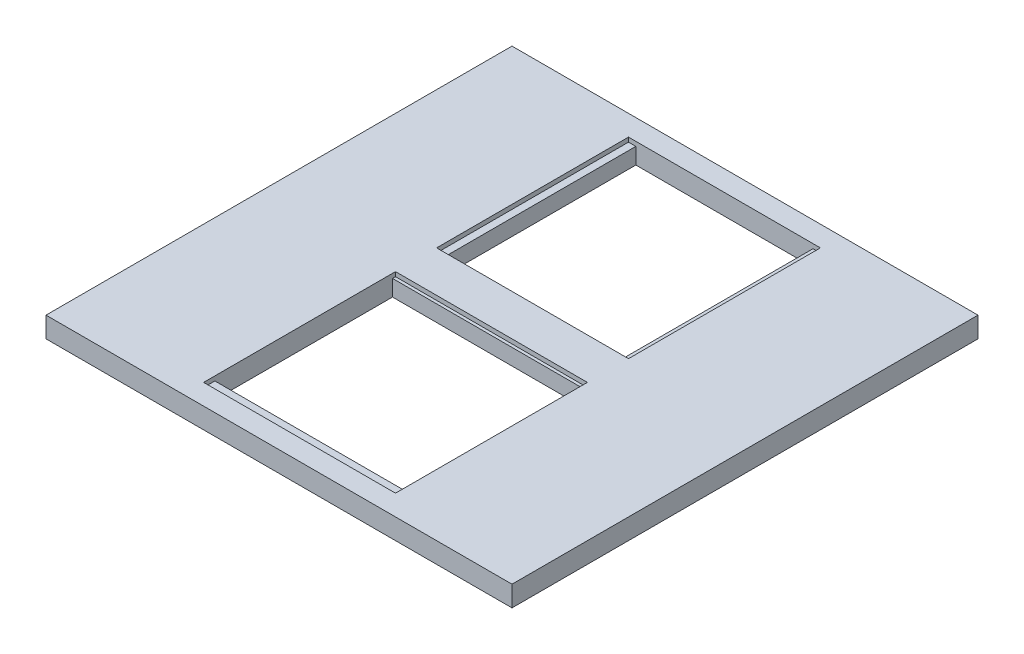
SolidWorks part; units mm, degrees
ref_plane "Front Plane" through (0, 0, 0) normal (0, 0, 1) x (1, 0, 0)
ref_plane "Top Plane" through (0, 0, 0) normal (0, 1, 0) x (1, 0, 0)
ref_plane "Right Plane" through (0, 0, 0) normal (1, 0, 0) x (0, 0, -1)
sketch "Sketch1" plane through (0, 0, 0) normal (0, 1, 0) x (1, 0, 0)
  line L1 (-85, -85) -> (85, -85)
  line L2 (-85, -85) -> (-85, 85)
  line L3 (-85, 85) -> (85, 85)
  line L4 (85, -85) -> (85, 85)
  line L5 (-85, -85) -> (85, 85) construction
  line L6 (-85, 85) -> (85, -85) construction
  point P0 (0, 0)
  dimension "D1" = 170
  dimension "D2" = 170
extrude "Base" add sketch "Sketch1" along normal blind 7.5
sketch "Sketch2" plane through (0, 7.5, 0) normal (0, 1, 0) x (1, 0, 0)
  line L0 (0, -55) -> (0, 55) construction
  line L1 (-35, 7.5) -> (35, 7.5)
  line L2 (-35, 7.5) -> (-35, 77.5)
  line L3 (-35, 77.5) -> (35, 77.5)
  line L4 (35, 7.5) -> (35, 77.5)
  line L5 (-35, 7.5) -> (35, 77.5) construction
  line L6 (-35, 77.5) -> (35, 7.5) construction
  line L7 (0, -8.4673) -> (0, 8.4673) construction
  line L8 (-85, 85) -> (85, 0) construction
  line L9 (85, -85) -> (85, 85) construction
  line L10 (85, 85) -> (-85, 0) construction
  line L11 (-85, 85) -> (-85, -85) construction
  point P1 (0, 42.5)
  point P20 (0, 37.5)
  dimension "D1" = 70
  dimension "D2" = 70
extrude "Slot-1" cut sketch "Sketch2" against normal blind 1.6
sketch "Sketch3" plane through (0, 5.9, 0) normal (0, 1, 0) x (1, 0, 0)
  line L6 (-32.3269, 7.5) -> (32.3269, 7.5)
  line L7 (-32.3269, 7.5) -> (-32.3269, 77.5)
  line L8 (-32.3269, 77.5) -> (32.3269, 77.5)
  line L9 (32.3269, 7.5) -> (32.3269, 77.5)
  line L10 (-32.3269, 7.5) -> (32.3269, 77.5) construction
  line L11 (-32.3269, 77.5) -> (32.3269, 7.5) construction
  line L12 (-35, 77.5) -> (35, 7.5) construction
  line L13 (-35, 7.5) -> (35, 77.5) construction
  line L16 (-35, 7.5) -> (35, 7.5) construction
  line L17 (35, 77.5) -> (-35, 77.5) construction
  point P2 (0, 37.5)
  point P4 (0, 42.5)
  point P8 (0, 42.5)
  point P15 (0, 45.894)
  point P16 (29.0842, 70.0664)
  point P17 (0, 54.093)
  point P18 (-33.4926, 77.5)
  point P19 (-32.3269, 77.5)
  point P21 (33.0822, 77.494)
  point P22 (31.6212, 78.804)
  point P23 (-31.7606, 10.894)
  point P26 (-32.4752, 80.894)
  point P29 (0, 37.5)
extrude "Slot-1-Components" cut sketch "Sketch3" against normal up to surface (5.9 mm away) up to face at (0, 0, 0)
sketch "Sketch4" plane through (0, 7.5, 0) normal (0, 1, 0) x (1, 0, 0)
  line L0 (0, -8.4673) -> (0, 8.4673) construction
  line L1 (-35, -77.5) -> (35, -77.5)
  line L2 (-35, -77.5) -> (-35, -7.5)
  line L3 (-35, -7.5) -> (35, -7.5)
  line L4 (35, -77.5) -> (35, -7.5)
  line L5 (-35, -77.5) -> (35, -7.5) construction
  line L6 (-35, -7.5) -> (35, -77.5) construction
  line L7 (-85, -85) -> (85, 0) construction
  line L9 (85, -85) -> (85, 85) construction
  line L10 (85, -85) -> (-85, 0) construction
  line L12 (-85, 85) -> (-85, -85) construction
  point P0 (0, -42.5)
  point P12 (-85, 0)
  point P18 (-85, 0)
  point P19 (85, 0)
  point P21 (0, -38.0437)
  point P22 (0, -42.5)
  dimension "D1" = 70
  dimension "D2" = 70
extrude "Slot-2" cut sketch "Sketch4" against normal up to surface (1.6 mm away) up to face at (-33.6634, 5.9, -42.5)
sketch "Sketch6" plane through (0, 5.9, 0) normal (0, 1, 0) x (1, 0, 0)
  line L0 (0, -7.0923) -> (0, 7.0923) construction
  line L1 (-35, -8.5903) -> (35, -8.5903)
  line L2 (-35, -8.5903) -> (-35, -73.4035)
  line L3 (-35, -73.4035) -> (35, -73.4035)
  line L4 (35, -8.5903) -> (35, -73.4035)
  line L5 (-35, -8.5903) -> (35, -73.4035) construction
  line L6 (-35, -73.4035) -> (35, -8.5903) construction
  line L8 (-35, -7.5) -> (-35, -77.5) construction
  point P0 (0, -40.9969)
  point P7 (-35, -8.9645)
  point P9 (0, 0)
  point P11 (-35, -73.4035)
extrude "Slot-2-Components" cut sketch "Sketch6" against normal up to surface (5.9 mm away) up to face at (0, 0, -42.5)
